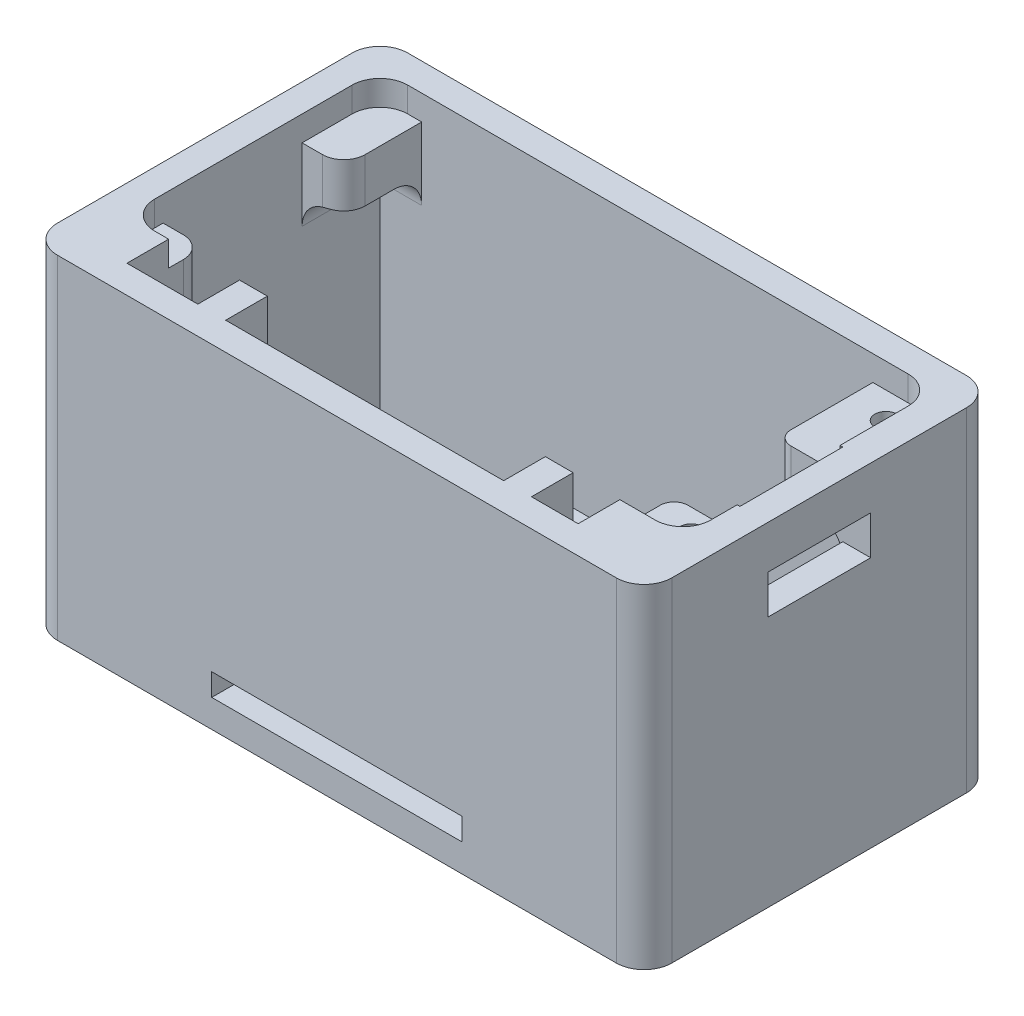
SolidWorks part; units mm, degrees
ref_plane "Front Plane" through (0, 0, 0) normal (0, 0, 1) x (1, 0, 0)
ref_plane "Top Plane" through (0, 0, 0) normal (0, 1, 0) x (1, 0, 0)
ref_plane "Right Plane" through (0, 0, 0) normal (1, 0, 0) x (0, 0, -1)
sketch "Sketch1" plane through (0, 0, 0) normal (0, 1, 0) x (1, 0, 0)
  line L1 (-28.067, -16.002) -> (28.067, -16.002)
  line L2 (-28.067, -16.002) -> (-28.067, 16.002)
  line L3 (-28.067, 16.002) -> (28.067, 16.002)
  line L4 (28.067, -16.002) -> (28.067, 16.002)
  line L5 (-28.067, -16.002) -> (28.067, 16.002) construction
  line L6 (-28.067, 16.002) -> (28.067, -16.002) construction
  point P0 (0, 0)
  dimension "D1" = 56.134
  dimension "D2" = 32.004
extrude "Boss-Extrude1" add sketch "Sketch1" along normal blind 30.48
shell "Shell1" thickness 2.54 removed face at (0, 30.48, 0)
sketch "Sketch2" plane through (0, 0, 0) normal (0, -1, 0) x (1, 0, 0)
  line L0 (0, 0) -> (36.576, 0) construction
  line L1 (28.067, 16.002) -> (28.067, -16.002) construction
  line L2 (23.622, -6.477) -> (12.954, -6.477)
  line L3 (23.622, -6.477) -> (23.622, 6.477)
  line L4 (23.622, 6.477) -> (12.954, 6.477)
  line L5 (12.954, -6.477) -> (12.954, 6.477)
  line L6 (23.622, -6.477) -> (12.954, 6.477) construction
  line L7 (23.622, 6.477) -> (12.954, -6.477) construction
  point P3 (18.288, 0)
  dimension "D1" = 12.954
  dimension "D2" = 10.668
  dimension "D3" = 4.445
extrude "Cut-Extrude1" cut sketch "Sketch2" against normal up to surface (2.54 mm away) up to face at (0, 2.54, 0)
sketch "Sketch3" plane through (0, 30.48, 0) normal (0, 1, 0) x (1, 0, 0)
  line L0 (0, 0) -> (-37.2945, 0) construction
  line L1 (-25.527, 13.462) -> (-25.527, -13.462) construction
  line L17 (-25.527, 13.462) -> (-25.527, 6.35)
  line L19 (-21.717, 13.462) -> (-21.717, 8.3058)
  line L20 (-23.6728, 6.35) -> (-25.527, 6.35)
  line L21 (-21.717, -13.462) -> (-21.717, -8.3058)
  line L22 (-23.6728, -6.35) -> (-25.527, -6.35)
  line L23 (-25.527, -13.462) -> (-25.527, -6.35)
  line L24 (-21.717, -13.462) -> (-25.527, -13.462)
  line L25 (25.527, 13.462) -> (-25.527, 13.462) construction
  line L26 (25.527, 13.462) -> (19.5072, 13.462)
  line L27 (19.5072, 13.462) -> (19.5072, 5.969)
  line L28 (25.527, 4.699) -> (25.527, 13.462)
  line L29 (25.527, -13.462) -> (25.527, 13.462) construction
  line L30 (-25.527, 13.462) -> (-21.717, 13.462)
  line L34 (25.527, -13.462) -> (25.527, 13.462) construction
  line L35 (25.527, 4.699) -> (20.7772, 4.699)
  line L36 (25.527, -4.699) -> (25.527, -13.462)
  line L37 (25.527, -13.462) -> (19.5072, -13.462)
  line L38 (19.5072, -13.462) -> (19.5072, -5.969)
  line L39 (25.527, -4.699) -> (20.7772, -4.699)
  arc A6 (-21.717, 8.3058) -> (-23.6728, 6.35) centre (-23.6728, 8.3058) cw
  arc A7 (-21.717, -8.3058) -> (-23.6728, -6.35) centre (-23.6728, -8.3058) ccw
  arc A10 (19.5072, 5.969) -> (20.7772, 4.699) centre (20.7772, 5.969) ccw
  arc A11 (19.5072, -5.969) -> (20.7772, -4.699) centre (20.7772, -5.969) cw
  dimension "D2" = 12.7
  dimension "D3" = 1.9558
  dimension "D5" = 1.27
  dimension "D1" = 3.81
  dimension "D4" = 9.398
  dimension "D6" = 44.45
extrude "Boss-Extrude2" add sketch "Sketch3" against normal blind 6.35
fillet "Fillet2" radius 2.54 4 edges at (28.067, 15.24, 16.002) (28.067, 15.24, -16.002) (-28.067, 15.24, -16.002) (-28.067, 15.24, 16.002)
fillet "Fillet3" radius 2.54 8 edges at (-25.527, 24.13, 9.906) (-23.622, 24.13, 13.462) (22.5171, 24.13, 13.462) (25.527, 24.13, 9.0805) (-23.622, 24.13, -13.462) (-25.527, 24.13, -9.906) (22.5171, 24.13, -13.462) (25.527, 24.13, -9.0805)
sketch "Sketch10" plane through (0, 0, -16.002) normal (0, 0, -1) x (-1, 0, 0)
  line L0 (-25.527, 0) -> (25.527, 0) construction
  line L1 (-11.43, 2.54) -> (11.43, 2.54)
  line L2 (-11.43, 2.54) -> (-11.43, 4.572)
  line L3 (-11.43, 4.572) -> (11.43, 4.572)
  line L4 (11.43, 2.54) -> (11.43, 4.572)
  point P4 (0, 2.54)
  dimension "D1" = 2.54
  dimension "D2" = 2.032
  dimension "D3" = 22.86
sketch "Sketch12" plane through (0, 0, 0) normal (0, -1, 0) x (1, 0, 0)
  line L0 (-28.067, -13.462) -> (-28.067, 13.462) construction
  line L1 (-20.447, 10.287) -> (-17.907, 10.287)
  line L2 (-20.447, 10.287) -> (-20.447, -10.287)
  line L3 (-20.447, -10.287) -> (-17.907, -10.287)
  line L4 (-17.907, 10.287) -> (-17.907, -10.287)
  point P4 (-17.907, 0)
  dimension "D1" = 2.54
  dimension "D2" = 20.574
  dimension "D3" = 7.62
extrude "Cut-Extrude8" cut sketch "Sketch12" against normal up to surface (2.54 mm away) up to face at (18.288, 2.54, 0)
extrude "Cut-Extrude9" cut sketch "Sketch10" against normal up to surface (32.004 mm away) contours L3 L4 L1 L2 up to face at (0, 15.24, 16.002)
sketch "Sketch13" plane through (0, 30.48, 0) normal (0, 1, 0) x (1, 0, 0)
  line L0 (-21.717, -13.462) -> (19.5072, -13.462) construction
  line L1 (-15.24, -13.462) -> (-12.7, -13.462)
  line L2 (-15.24, -13.462) -> (-15.24, -9.652)
  line L3 (-15.24, -9.652) -> (-12.7, -9.652)
  line L4 (-12.7, -13.462) -> (-12.7, -9.652)
  line L5 (0, 0) -> (0, -20.8868) construction
  dimension "D1" = 3.81
  dimension "D2" = 2.54
  dimension "D3" = 25.4
extrude "Boss-Extrude3" add sketch "Sketch13" against normal up to surface (27.94 mm away)
mirror "Mirror1" about plane through (0, 0, 0) normal (1, 0, 0) of "Boss-Extrude3"
sketch "Sketch14" plane through (12.7, 0, 0) normal (-1, 0, 0) x (0, 0, 1)
  line L0 (9.652, 2.54) -> (9.652, 30.48) construction
  line L1 (9.652, 4.572) -> (13.462, 4.572)
  line L2 (9.652, 4.572) -> (9.652, 5.842)
  line L3 (9.652, 5.842) -> (13.462, 5.842)
  line L4 (13.462, 4.572) -> (13.462, 5.842)
  line L5 (13.462, 2.54) -> (13.462, 30.48) construction
  line L6 (13.462, 2.54) -> (9.652, 2.54) construction
  dimension "D1" = 1.27
  dimension "D2" = 2.032
extrude "Boss-Extrude4" add sketch "Sketch14" along normal up to surface (25.4 mm away) up to face at (-12.7, 16.51, 11.557)
sketch "Sketch15" plane through (0, 30.48, 0) normal (0, 1, 0) x (1, 0, 0)
  line L0 (-25.527, -7.112) -> (-25.527, 10.922)
  line L1 (-22.987, 13.462) -> (22.733, 13.462)
  line L2 (-25.527, 13.462) -> (-25.527, -13.462) construction
  line L3 (25.273, -7.112) -> (25.273, 4.8106)
  line L4 (25.273, 10.922) -> (25.273, -1.0006)
  line L5 (0, 1.905) -> (-34.1825, 1.905) construction
  line L6 (-22.987, -9.652) -> (22.733, -9.652)
  line L7 (-12.7, -9.652) -> (12.7, -9.652) construction
  arc A0 (-25.527, 10.922) -> (-22.987, 13.462) centre (-22.987, 10.922) cw
  arc A1 (22.733, 13.462) -> (25.273, 10.922) centre (22.733, 10.922) cw
  arc A2 (-25.527, -7.112) -> (-22.987, -9.652) centre (-22.987, -7.112) ccw
  arc A3 (22.733, -9.652) -> (25.273, -7.112) centre (22.733, -7.112) ccw
  point P2 (-21.4258, 13.97)
  point P8 (-25.527, 1.905)
  line M14 (-25.527, 6.35) -> (-23.6728, 6.35)
  arc M15 (-23.6728, 6.35) -> (-21.717, 8.3058) centre (-23.6728, 8.3058) ccw
  line M16 (-21.717, 8.3058) -> (-21.717, 13.462)
  line M17 (-21.717, 13.462) -> (19.5072, 13.462)
  line M18 (19.5072, 13.462) -> (19.5072, 5.969)
  arc M19 (19.5072, 5.969) -> (20.7772, 4.699) centre (20.7772, 5.969) ccw
  line M20 (20.7772, 4.699) -> (25.527, 4.699)
  line M31 (25.527, -4.699) -> (20.7772, -4.699)
  arc M32 (20.7772, -4.699) -> (19.5072, -5.969) centre (20.7772, -5.969) ccw
  line M33 (19.5072, -5.969) -> (19.5072, -13.462)
  line M43 (-21.717, -13.462) -> (-21.717, -8.3058)
  arc M44 (-21.717, -8.3058) -> (-23.6728, -6.35) centre (-23.6728, -8.3058) ccw
  line M45 (-23.6728, -6.35) -> (-25.527, -6.35)
  dimension "D3" = 2.54
  dimension "D1" = 23.114
  dimension "D2" = 50.8
extrude "Cut-Extrude10" cut sketch "Sketch15" against normal blind 2.286 contours A1 L1 A0 L0 L3 L4 M14 M15 M16 M17 M18 M19 M20 | L6 A3 L3 M31 M32 M33 | L0 A2 L6 M43 M44 M45 | A0 L0 L1 M14 M15 M16 region at (-23.5597, 30.48, 7.9525) region at (-23.596, 30.48, -9.8426) region at (22.3041, 30.48, 7.1053) region at (22.3428, 30.48, -9.0013)
sketch "Sketch16" plane through (0, 0, 0) normal (1, 0, 0) x (0, 0, -1)
  line L1 (-4.699, 22.987) -> (4.699, 22.987)
  line L2 (-4.699, 22.987) -> (-4.699, 26.543)
  line L3 (-4.699, 26.543) -> (4.699, 26.543)
  line L4 (4.699, 22.987) -> (4.699, 26.543)
  line L5 (-4.699, 22.987) -> (4.699, 26.543) construction
  line L6 (-4.699, 26.543) -> (4.699, 22.987) construction
  line L7 (-13.462, 30.48) -> (13.462, 30.48) construction
  point P0 (0, 24.765)
  dimension "D1" = 3.556
  dimension "D2" = 9.398
  dimension "D3" = 3.937
extrude "Cut-Extrude11" cut sketch "Sketch16" along normal up to surface (28.067 mm away) up to face at (28.067, 15.24, 0)
sketch "Sketch11" plane through (0, 30.48, 0) normal (0, 1, 0) x (1, 0, 0)
  line L0 (25.273, 4.699) -> (25.273, 10.922) construction
  line L1 (23.114, 11.049) -> (23.114, -6.731) construction
  line L2 (19.5072, 13.462) -> (22.733, 13.462) construction
  circle A0 centre (23.114, 11.049) radius 1.016
  circle A1 centre (23.114, -6.731) radius 1.016
  point P6 (23.114, 10.1847)
  dimension "D2" = 2.032
  dimension "D4" = 2.413
  dimension "D1" = 17.78
  dimension "D3" = 2.159
extrude "Cut-Extrude12" cut sketch "Sketch11" against normal blind 9.398 contours A1 | A0 region at (23.114, 30.48, 6.731)
